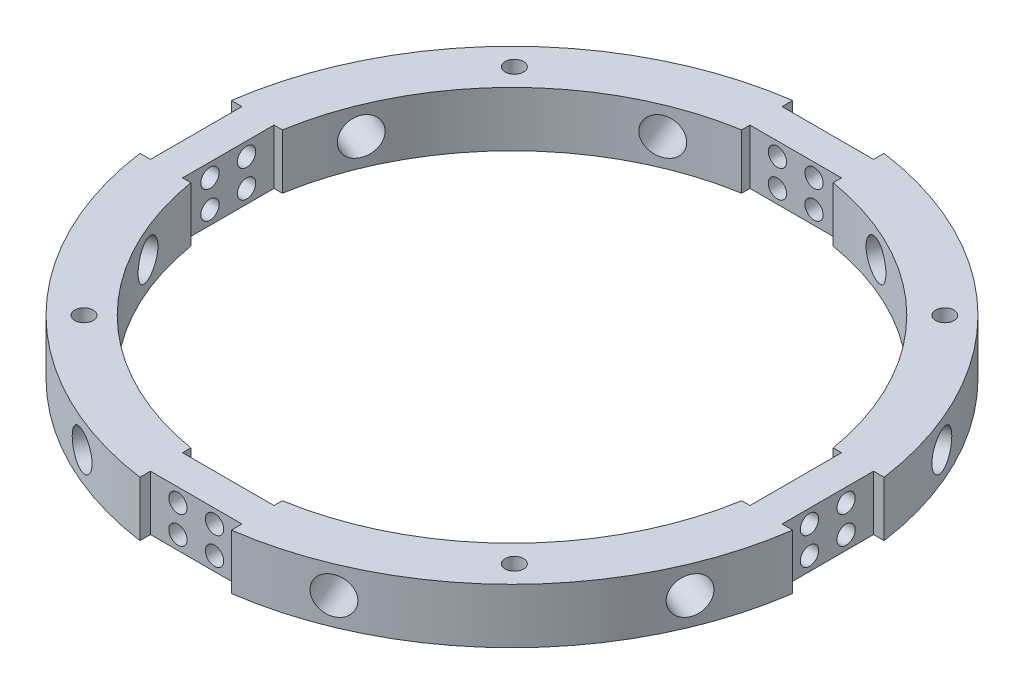
SolidWorks part; units mm, degrees
ref_plane "Front Plane" through (0, 0, 0) normal (0, 0, 1) x (1, 0, 0)
ref_plane "Top Plane" through (0, 0, 0) normal (0, 1, 0) x (1, 0, 0)
ref_plane "Right Plane" through (0, 0, 0) normal (1, 0, 0) x (0, 0, -1)
sketch "Sketch1" plane through (0, 0, 0) normal (0, 1, 0) x (1, 0, 0)
  circle A0 centre (0, 0) radius 72
  circle A1 centre (0, 0) radius 61
  dimension "OuterDiameter" = 144
  dimension "InnerDiameter" = 122
extrude "Boss-Extrude1" add sketch "Sketch1" along normal blind 6 and the other way blind 6
sketch "Sketch5" plane through (0, 6, 0) normal (0, 1, 0) x (1, 0, 0)
  line L0 (0, 0) -> (53.7588, 53.7588) construction
  line L1 (0.2616, 0.2616) -> (47.2842, 47.2842) construction
  line L2 (-121.3123, 0) -> (150.1577, 0) construction
  circle A0 centre (47.2842, 47.2842) radius 2
  circle A1 centre (47.2842, -46.761) radius 2
  circle A2 centre (-46.761, -46.761) radius 2
  circle A3 centre (-46.761, 47.2842) radius 2
  dimension "MountingBoltDiameter" = 4
  dimension "D2" = 66.5
  dimension "D3" = 45
  dimension "D1" = 4
extrude "Cut-Extrude3" cut sketch "Sketch5" against normal through all
sketch "Sketch6" plane through (0, 6, 0) normal (0, 1, 0) x (1, 0, 0)
  line L0 (0, -83.4209) -> (0, 77.0416) construction
  line L1 (-88.8703, 0) -> (103.6253, 0) construction
  line L2 (-10, -69) -> (10, -69)
  line L3 (-10, 72) -> (10, 72)
  line L4 (-10, 72) -> (-10, 69)
  line L5 (-10, 69) -> (10, 69)
  line L6 (10, 72) -> (10, 69)
  line L7 (-10, 72) -> (10, 69) construction
  line L8 (-10, 69) -> (10, 72) construction
  line L9 (10, -72) -> (10, -69)
  line L10 (-10, -72) -> (10, -72)
  line L11 (-10, -72) -> (-10, -69)
  line L12 (0, 0) -> (60.635, 60.635) construction
  line L13 (69, -10) -> (69, 10)
  line L14 (72, 10) -> (69, 10)
  line L15 (72, -10) -> (72, 10)
  line L16 (72, -10) -> (69, -10)
  line L17 (-72, -10) -> (-69, -10)
  line L18 (-72, -10) -> (-72, 10)
  line L19 (-72, 10) -> (-69, 10)
  line L20 (-69, -10) -> (-69, 10)
  point P5 (0, 70.5)
  point P10 (0, 72)
  dimension "RailWidth" = 20
  dimension "D1" = 72
  dimension "D2" = 3
extrude "Cut-Extrude4" cut sketch "Sketch6" against normal through all
sketch "Sketch12" plane through (0, 0, 69) normal (0, 0, 1) x (1, 0, 0)
  line L0 (0, 13.7216) -> (0, -16.0459) construction
  line L1 (-75.3828, 0) -> (78.5537, 0) construction
  circle A4 centre (4, 3) radius 2
  circle A5 centre (-4, 3) radius 2
  circle A6 centre (4, -3) radius 2
  circle A7 centre (-4, -3) radius 2
  point P15 (0, 0)
  dimension "D3" = 4
  dimension "D4" = 4
  dimension "D1" = 4
  dimension "D2" = 4
  dimension "D5" = 4
  dimension "D6" = 4
  dimension "D7" = 4
  dimension "D8" = 4
  dimension "D9" = 3
  dimension "D10" = 3
  dimension "D11" = 3
  dimension "D12" = 3
extrude "Cut-Extrude8" cut sketch "Sketch12" against normal through all
sketch "Sketch13" plane through (0, 6, 0) normal (0, 1, 0) x (1, 0, 0)
  line L0 (0, -87.0356) -> (0, 86.4553) construction
  line L1 (-98.9563, 0) -> (122.4152, 0) construction
  line L2 (0, 0) -> (105.5387, 105.5387) construction
  line L3 (-10, -62) -> (10, -62)
  line L4 (-10, -62) -> (-10, -59)
  line L5 (-10, -59) -> (10, -59)
  line L6 (10, -62) -> (10, -59)
  line L7 (-10, -62) -> (10, -59) construction
  line L8 (-10, -59) -> (10, -62) construction
  line L9 (-10, 59) -> (10, 59)
  line L10 (10, 62) -> (10, 59)
  line L11 (-10, 62) -> (10, 62)
  line L12 (-10, 62) -> (-10, 59)
  line L13 (-59, -10) -> (-59, 10)
  line L14 (-62, 10) -> (-59, 10)
  line L15 (-62, -10) -> (-62, 10)
  line L16 (-62, -10) -> (-59, -10)
  line L17 (62, -10) -> (59, -10)
  line L18 (62, -10) -> (62, 10)
  line L19 (62, 10) -> (59, 10)
  line L20 (59, -10) -> (59, 10)
  point P7 (0, -60.5)
  dimension "D1" = 20
  dimension "D3" = 59
  dimension "D2" = 62
  dimension "D4" = 45
extrude "Cut-Extrude9" cut sketch "Sketch13" against normal through all
sketch "Sketch14" plane through (0, 6, 0) normal (0, 1, 0) x (1, 0, 0)
  line L0 (0, 0) -> (-136.7554, 0) construction
  line L1 (0, 0) -> (0, 142.5403) construction
  line L2 (0, 0) -> (-49.7797, 120.1788) construction
  line L3 (0, 0) -> (-96.3261, 96.3261) construction
  line L4 (0, 0) -> (-120.1788, 49.7797) construction
  line L5 (0, 0) -> (-49.7797, -120.1788) construction
  line L6 (0, 0) -> (-120.1788, -49.7797) construction
  line L7 (0, 0) -> (49.7797, -120.1788) construction
  line L8 (0, 0) -> (120.1788, -49.7797) construction
  line L9 (0, 0) -> (120.1788, 49.7797) construction
  line L10 (0, 0) -> (49.7797, 120.1788) construction
  dimension "D1" = 22.5
ref_plane "Plane1" through (-49.7797, 6, -120.1788) normal (-0.3827, 0, -0.9239) x (-0.9239, 0, 0.3827)
ref_plane "Plane2" through (-120.1788, 6, -49.7797) normal (-0.9239, 0, -0.3827) x (-0.3827, 0, 0.9239)
ref_plane "Plane3" through (-120.1788, 6, 49.7797) normal (-0.9239, 0, 0.3827) x (0.3827, 0, 0.9239)
ref_plane "Plane4" through (-49.7797, 6, 120.1788) normal (-0.3827, 0, 0.9239) x (0.9239, 0, 0.3827)
sketch "Sketch15" plane through (-49.7797, 6, -120.1788) normal (-0.3827, 0, -0.9239) x (-0.9239, 0, 0.3827)
  line L0 (-120.7735, -6) -> (151.4229, -6) construction
  circle A0 centre (0, -6) radius 4
  dimension "D1" = 8
extrude "Cut-Extrude10" cut sketch "Sketch15" against normal through all
sketch "Sketch16" plane through (-120.1788, 6, -49.7797) normal (-0.9239, 0, -0.3827) x (-0.3827, 0, 0.9239)
  line L0 (-99.0113, -6) -> (114.7123, -6) construction
  circle A0 centre (0, -6) radius 4
  dimension "D1" = 8
extrude "Cut-Extrude11" cut sketch "Sketch16" against normal through all
sketch "Sketch17" plane through (-120.1788, 6, 49.7797) normal (-0.9239, 0, 0.3827) x (0.3827, 0, 0.9239)
  line L0 (-104.6958, -6) -> (121.5008, -6) construction
  circle A0 centre (0, -6) radius 4
  dimension "D1" = 8
extrude "Cut-Extrude12" cut sketch "Sketch17" against normal through all
sketch "Sketch18" plane through (-49.7797, 6, 120.1788) normal (-0.3827, 0, 0.9239) x (0.9239, 0, 0.3827)
  line L0 (-104.7035, -6) -> (121.0277, -6) construction
  circle A0 centre (0, -6) radius 4
  dimension "D1" = 8
extrude "Cut-Extrude13" cut sketch "Sketch18" against normal through all
sketch "Sketch19" plane through (69, 0, 0) normal (1, 0, 0) x (0, 0, -1)
  line L0 (0, 13.2441) -> (0, -16.5234) construction
  line L1 (-73.8627, 0) -> (80.0739, 0) construction
  line L2 (10, 6) -> (-10, 6) construction
  line L3 (-10, -6) -> (-10, 6) construction
  circle A0 centre (4, 3) radius 2
  circle A1 centre (-4, 3) radius 2
  circle A2 centre (4, -3) radius 2
  circle A3 centre (-4, -3) radius 2
  dimension "D3" = 4
  dimension "D4" = 4
  dimension "D1" = 4
  dimension "D2" = 4
  dimension "D5" = 4
  dimension "D6" = 4
  dimension "D7" = 4
  dimension "D8" = 4
  dimension "D9" = 3
  dimension "D10" = 3
  dimension "D11" = 3
  dimension "D12" = 3
  dimension "D13" = 6
  dimension "D14" = 10
extrude "Cut-Extrude14" cut sketch "Sketch19" against normal through all
equation "\"InternalDiameter\" = 122mm"
equation "\"ExternalDiameter\"= 144mm"
equation "\"InnerDiameter@Sketch1\"= \"InternalDiameter\""
equation "\"OuterDiameter@Sketch1\"= \"ExternalDiameter\""
equation "\"MountingBoltDiameter\"= 4mm"
equation "\"NumberOfMountingBolts\"= 4"
equation "\"MountingBoltDiameter@Sketch5\"= \"MountingBoltDiameter\""
equation "\"D1@Sketch5\"= \"NumberOfMountingBolts\""
equation "\"D2@Sketch5\"= 0.25 * ( \"InternalDiameter\" + \"ExternalDiameter\" )"
equation "\"RailBoltDiameter\"= 6mm"
equation "\"RailBoltSpacing\"= 12mm"
equation "\"RailWidth\"= 10mm"
equation "\"RailWidth@Sketch6\"= \"RailWidth\" * 2"
equation "\"D1@Sketch13\"= \"RailWidth\" * 2"
equation "\"RailDepth\"= 2mm"
equation "\"D3@Sketch13\"= \"InternalDiameter\" / 2 - \"RailDepth\""
equation "\"D2@Sketch13\"= \"InternalDiameter\" / 2 + \"RailDepth\" / 2"
equation "\"D1@Sketch6\"= \"ExternalDiameter\" / 2"
equation "\"D2@Sketch6\"= \"RailDepth\" * 1.5"
equation "\"TurnLockAngularOffset\"= 22.5"
equation "\"D1@Sketch14\"= \"TurnLockAngularOffset\""
equation "\"TurnLockDiameter\"= 8mm"
equation "\"D1@Sketch16\"= \"TurnLockDiameter\""
equation "\"D1@Sketch15\"= \"TurnLockDiameter\""
equation "\"D1@Sketch17\"= \"TurnLockDiameter\""
equation "\"D1@Sketch18\"= \"TurnLockDiameter\""
equation "\"D1@Sketch12\"= \"MountingBoltDiameter\""
equation "\"D8@Sketch12\"= \"D1@Sketch12\""
equation "\"D7@Sketch12\"= \"D8@Sketch12\""
equation "\"D2@Sketch12\"= \"D7@Sketch12\""
equation "\"D12@Sketch12\"= \"D2@Sketch12\" * 3 / 4"
equation "\"D3@Sketch12\"= \"D2@Sketch12\""
equation "\"D11@Sketch12\"= \"D12@Sketch12\""
equation "\"D6@Sketch12\"= \"D3@Sketch12\""
equation "\"D5@Sketch12\"= \"D6@Sketch12\""
equation "\"D4@Sketch12\"= \"D5@Sketch12\""
equation "\"D10@Sketch12\"= \"D4@Sketch12\" * 3 / 4"
equation "\"D9@Sketch12\"= \"D10@Sketch12\""
equation "\"D14@Sketch19\"= \"RailWidth\""
equation "\"D13@Sketch19\"= 6mm"
equation "\"D2@Sketch19\"= \"D4@Sketch12\""
